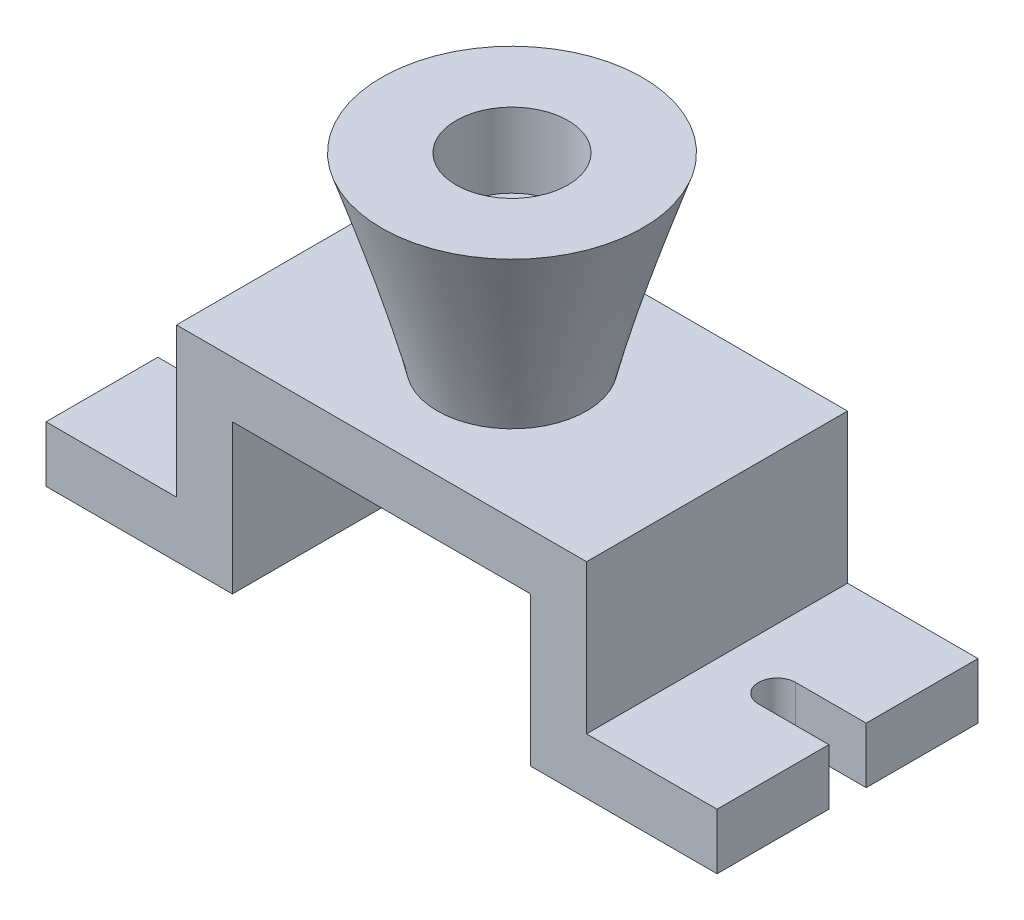
SolidWorks part; units mm, degrees
ref_plane "Front Plane" through (0, 0, 0) normal (0, 0, 1) x (1, 0, 0)
ref_plane "Top Plane" through (0, 0, 0) normal (0, 1, 0) x (1, 0, 0)
ref_plane "Right Plane" through (0, 0, 0) normal (1, 0, 0) x (0, 0, -1)
sketch "Sketch1" plane through (0, 0, 0) normal (0, 0, 1) x (1, 0, 0)
  line L0 (0, 86.6505) -> (0, -88.3981) construction
  line L1 (-166.0194, 0) -> (-46.0194, 0) construction
  line L2 (-46.0194, 0) -> (-46.0194, 40)
  line L3 (-96.0194, 0) -> (-96.0194, 15)
  line L4 (-96.0194, 15) -> (-61.0194, 15)
  line L5 (-61.0194, 15) -> (-61.0194, 55)
  line L6 (-61.0194, 55) -> (48.9806, 55)
  line L7 (48.9806, 55) -> (48.9806, 15)
  line L8 (48.9806, 15) -> (83.9806, 15)
  line L9 (83.9806, 15) -> (83.9806, 0)
  line L10 (83.9806, 0) -> (33.9806, 0)
  line L11 (-46.0194, 40) -> (33.9806, 40)
  line L12 (33.9806, 40) -> (33.9806, 0)
  line L13 (33.9806, 0) -> (153.7864, 0) construction
  line L14 (-46.0194, 0) -> (-96.0194, 0)
  dimension "D1" = 50
  dimension "D2" = 15
  dimension "D3" = 50
  dimension "D4" = 80
  dimension "D5" = 15
  dimension "D6" = 15
  dimension "D7" = 55
  dimension "D8" = 15
  dimension "D9" = 15
  dimension "D10" = 33.9806
extrude "Boss-Extrude1" add sketch "Sketch1" along normal mid plane 70
sketch "Sketch2" plane through (0, 15, 0) normal (0, 1, 0) x (1, 0, 0)
  line L0 (-6.0194, 100.3298) -> (-6.0194, -97.7793) construction
  line L1 (65.0875, 5) -> (83.9806, 5)
  line L2 (83.9806, -35) -> (83.9806, 35) construction
  line L3 (65.0875, -5) -> (83.9806, -5)
  line L4 (83.9806, -5) -> (83.9806, 5)
  line L5 (-96.0194, -5) -> (-96.0194, 5)
  line L6 (-77.1264, -5) -> (-96.0194, -5)
  line L7 (-77.1264, 5) -> (-96.0194, 5)
  arc A0 (65.0875, 5) -> (65.0875, -5) centre (65.0875, 0) ccw
  arc A1 (-77.1264, 5) -> (-77.1264, -5) centre (-77.1264, 0) cw
  dimension "D1" = 10
extrude "Cut-Extrude1" cut sketch "Sketch2" against normal blind 70
sketch "Sketch3" plane through (0, 55, 0) normal (0, 1, 0) x (1, 0, 0)
  circle A0 centre (-6.0194, 0) radius 20
  dimension "D1" = 40
ref_plane "Plane1" through (0, 105, 0) normal (0, 1, 0) x (1, 0, 0)
sketch "Sketch4" plane through (0, 105, 0) normal (0, 1, 0) x (1, 0, 0)
  circle A0 centre (-6.0194, 0) radius 35
  dimension "D1" = 70
loft "Loft1" add profiles "Sketch4", "Sketch3" connector at (-38.2925, 105, 13.5443) connector at (-26.0082, 55, -0.6689)
sketch "Sketch11" plane through (0, 105, 0) normal (0, 1, 0) x (1, 0, 0)
  circle A0 centre (-6.0194, 0) radius 15
  dimension "D1" = 30
extrude "Cut-Extrude2" cut sketch "Sketch11" against normal blind 20 contours A0
sketch "Sketch12" plane through (0, 40, 0) normal (0, -1, 0) x (1, 0, 0)
  circle A0 centre (-6.0194, 0) radius 8
  dimension "D1" = 16
extrude "Cut-Extrude3" cut sketch "Sketch12" against normal blind 30 contours A0
sketch "Sketch13" plane through (0, 85, 0) normal (0, 1, 0) x (1, 0, 0)
  circle A0 centre (-6.0194, 0) radius 8
  dimension "D1" = 16
extrude "Cut-Extrude4" cut sketch "Sketch13" against normal blind 30
